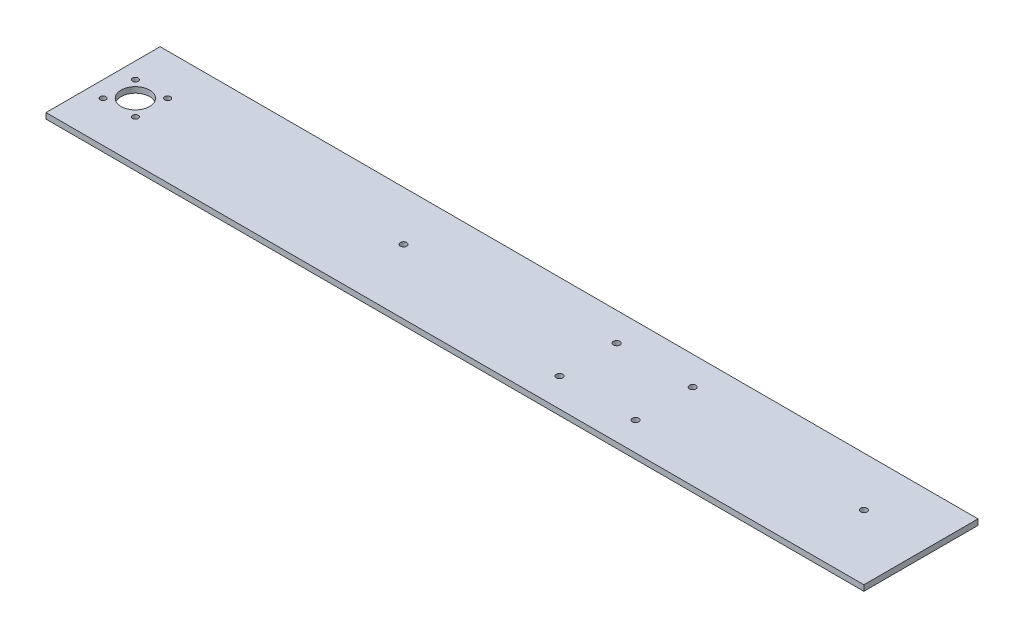
SolidWorks part; units mm, degrees
material "3.0526 (EN-AW 3005)"
ref_plane "Płaszczyzna przednia" through (0, 0, 0) normal (0, 0, 1) x (1, 0, 0)
ref_plane "Płaszczyzna górna" through (0, 0, 0) normal (0, 1, 0) x (1, 0, 0)
ref_plane "Płaszczyzna prawa" through (0, 0, 0) normal (1, 0, 0) x (0, 0, -1)
sketch "Sketch1" plane through (0, 0, 0) normal (0, 1, 0) x (1, 0, 0)
  line L1 (-130, 0) -> (300, 0)
  line L2 (-130, 0) -> (-130, 60)
  line L3 (-130, 60) -> (300, 60)
  line L4 (300, 0) -> (300, 60)
  dimension "D1" = 430
  dimension "D2" = 60
extrude "Boss-Extrude1" add sketch "Sketch1" along normal blind 3
hole_wizard "Otwór pod śrubę M31" positions "Sketch2" profile "Sketch3" hole size "M3" standard "Ansi Metric" end condition through all
sketch "Sketch2" plane through (0, 3, 0) normal (0, 1, 0) x (1, 0, 0)
  line L0 (-130, 60) -> (-130, 0) construction
  line L1 (-130, 0) -> (300, 0) construction
  line L2 (300, 0) -> (300, 60) construction
  line L3 (300, 60) -> (-130, 60) construction
  point P0 (266, 34)
  point P2 (24, 34)
  point P20 (125, 15)
  point P22 (165, 15)
  point P24 (165, 45)
  point P26 (125, 45)
  dimension "D1" = 154
  dimension "D2" = 34
  dimension "D3" = 34
  dimension "D4" = 34
  dimension "D11" = 15
  dimension "D12" = 15
  dimension "D15" = 15
  dimension "D16" = 15
  dimension "D25" = 40
  dimension "D26" = 40
  dimension "D27" = 135
  dimension "D28" = 135
sketch "Sketch3" plane through (266, 3, -34) normal (1, 0, 0) x (0, 0, 1)
  line L0 (0, 0) -> (0, 3)
  line L1 (0, 3) -> (1.7, 3)
  line L2 (1.7, 3) -> (1.7, 0)
  line L5 (1.7, 0) -> (0, 0)
  line L11 (0, -6.35) -> (0, 107.95) construction
  dimension "Œrednica otworu na wylot" = 3.4
  dimension "G³êbokoœæ otworu na wylot" = 3
sketch "Sketch4" plane through (0, 3, 0) normal (0, 1, 0) x (1, 0, 0)
  line L0 (-130, 0) -> (300, 0) construction
  line L1 (-130, 60) -> (-130, 0) construction
  circle A0 centre (-113, 30) radius 7.5
  dimension "D1" = 30
  dimension "D2" = 15
  dimension "D3" = 17
extrude "Cut-Extrude1" cut sketch "Sketch4" against normal blind 5
hole_wizard "Ø3.0mm Dowel Hole1" positions "Sketch5" profile "Sketch6" hole size "Ø3.0" standard "ANSI Metric"
sketch "Sketch5" plane through (0, 3, 0) normal (0, 1, 0) x (1, 0, 0)
  point P0 (-104.5147, 21.5147)
  point P3 (-104.5147, 38.4853)
  point P6 (-121.4853, 21.5147)
  point P9 (-121.4853, 38.4853)
sketch "Sketch6" plane through (-104.5147, 3, -21.5147) normal (1, 0, 0) x (0, 0, 1)
  line L0 (0, 0) -> (0, 6.9013)
  line L1 (0, 6.9013) -> (1.5, 6)
  line L2 (1.5, 6) -> (1.5, 0)
  line L5 (1.5, 0) -> (0, 0)
  line L10 (0, 6.9013) -> (-1.5, 6) construction
  line L11 (0, -6.35) -> (0, 107.95) construction
  dimension "Hole Dia." = 3
  dimension "Hole Depth" = 6
  dimension "Drill Angle" = 118
